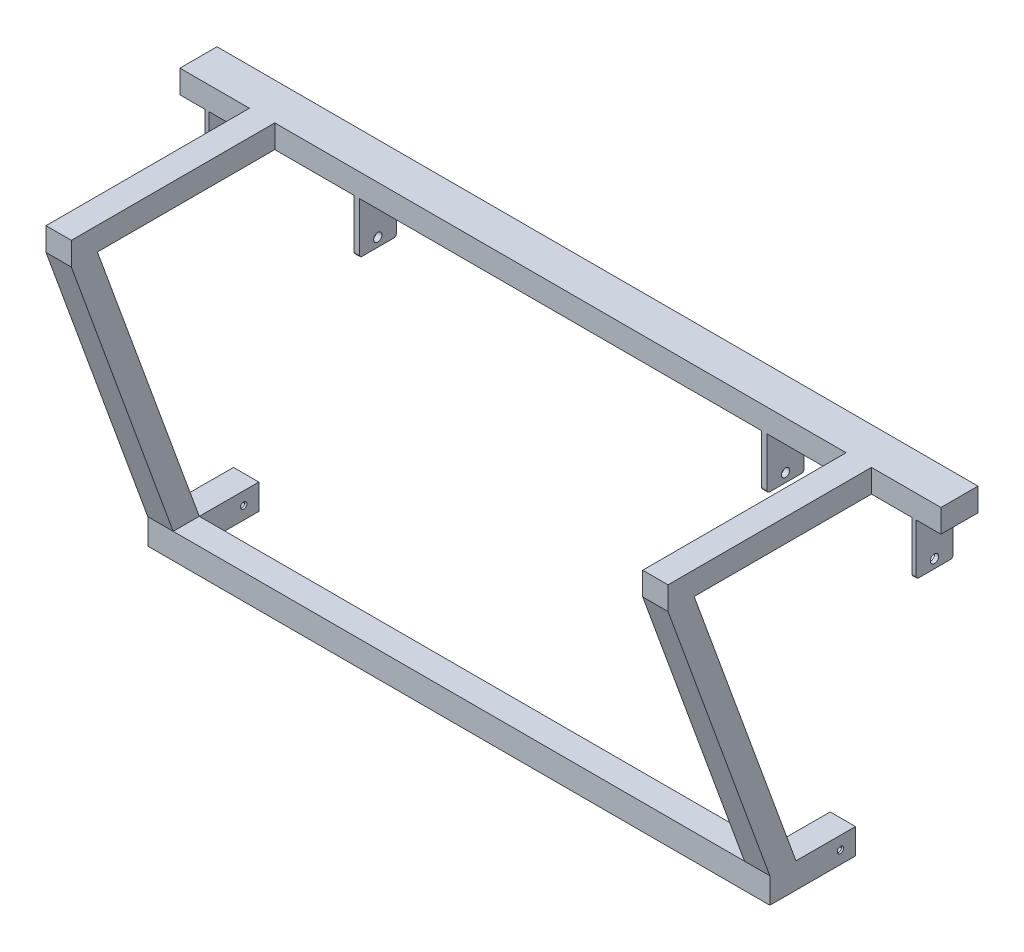
SolidWorks part; units mm, degrees
ref_plane "Front Plane" through (0, 0, 0) normal (0, 0, 1) x (1, 0, 0)
ref_plane "Top Plane" through (0, 0, 0) normal (0, 1, 0) x (1, 0, 0)
ref_plane "Right Plane" through (0, 0, 0) normal (1, 0, 0) x (0, 0, -1)
sketch "Sketch1" plane through (0, 0, 0) normal (0, 1, 0) x (1, 0, 0)
  line L1 (575, 28) -> (-575, 28)
  line L2 (575, 28) -> (575, -28)
  line L3 (575, -28) -> (-575, -28)
  line L4 (-575, 28) -> (-575, -28)
  line L5 (575, 28) -> (-575, -28) construction
  line L6 (575, -28) -> (-575, 28) construction
  point P0 (0, 0)
extrude "Boss-Extrude1" add sketch "Sketch1" against normal blind 35
sketch "Sketch2" plane through (0, 0, 28) normal (0, 0, 1) x (1, 0, 0)
  line L0 (0, -19.25) -> (0, 19.25) construction
  line L1 (-575, 0) -> (575, 0) construction
  line L2 (-470, 0) -> (-470, -35)
  line L3 (-575, -35) -> (575, -35) construction
  line L4 (-470, -35) -> (-431.7, -35)
  line L5 (-431.7, -35) -> (-431.7, 0)
  line L6 (-431.7, 0) -> (-470, 0)
  line L8 (431.7, 0) -> (470, 0)
  line L9 (431.7, -35) -> (431.7, 0)
  line L10 (470, -35) -> (431.7, -35)
  line L11 (470, 0) -> (470, -35)
extrude "Boss-Extrude2" add sketch "Sketch2" along normal blind 268
sketch "Sketch3" plane through (-470, 0, 0) normal (-1, 0, 0) x (0, 0, 1)
  line L0 (296, -35) -> (142.0909, -457.8617)
  line L2 (296, 0) -> (335.4, 0)
  line L3 (335.4, 0) -> (335.4, -35)
  line L4 (335.4, -35) -> (181.5154, -457.7945)
  line L6 (142.0909, -457.8617) -> (181.5154, -457.7945)
  line L7 (296, -35) -> (296, 0)
extrude "Boss-Extrude3" add sketch "Sketch3" against normal up to surface (38.3 mm away) up to face at (-431.7, -17.5, 162)
sketch "Sketch4" plane through (431.7, 0, 0) normal (-1, 0, 0) x (0, 0, 1)
  line L0 (296, 0) -> (335.4, 0)
  line L1 (335.4, 0) -> (335.4, -35)
  line L2 (335.4, -35) -> (181.5154, -457.7945)
  line L3 (181.5154, -457.7945) -> (142.0909, -457.8617)
  line L4 (142.0909, -457.8617) -> (296, -35)
  line L6 (296, 0) -> (296, -35)
extrude "Boss-Extrude4" add sketch "Sketch4" against normal up to surface (38.3 mm away) up to face at (470, -17.5, 162)
sketch "Sketch5" plane through (0, -458.1024, 0.7803) normal (0, -1, 0.0017) x (1, 0, 0)
  line L1 (470, 141.3109) -> (431.7, 141.3109)
  line L2 (470, 141.3109) -> (470, 180.7354)
  line L3 (470, 180.7354) -> (431.7, 180.7354)
  line L4 (431.7, 141.3109) -> (431.7, 180.7354)
extrude "Boss-Extrude5" add sketch "Sketch5" along normal blind 38.5
sketch "Sketch6" plane through (431.7, 0, 0) normal (-1, 0, 0) x (0, 0, 1)
  line L0 (142.0909, -457.8617) -> (181.5154, -457.7945)
  line L1 (181.5154, -457.7945) -> (181.581, -496.2945)
  line L2 (181.581, -496.2945) -> (142.1565, -496.3616)
  line L3 (142.1565, -496.3616) -> (142.0909, -457.8617)
extrude "Boss-Extrude6" add sketch "Sketch6" along normal up to surface (901.7 mm away) up to face at (-470, -145.808, 192.3438)
sketch "Sketch8" plane through (0, 0.2407, 141.3106) normal (0, -0.0017, -1) x (-1, 0, 0)
  line L0 (-470, -458.103) -> (-431.7, -458.103)
  line L1 (-431.7, -458.103) -> (-431.7, -496.603)
  line L2 (470, -496.603) -> (-470, -496.603) construction
  line L3 (-431.7, -496.603) -> (-470, -496.603)
  line L4 (-470, -496.603) -> (-470, -458.103)
  line L5 (0, 199.87) -> (0, -199.87) construction
  line L6 (431.7, -496.603) -> (470, -496.603)
  line L7 (431.7, -458.103) -> (431.7, -496.603)
  line L8 (470, -458.103) -> (431.7, -458.103)
  line L9 (470, -496.603) -> (470, -458.103)
extrude "Boss-Extrude7" add sketch "Sketch8" along normal blind 90
shell "Shell2" thickness 3 removed face at (-575, -17.5, 0)
sketch "Sketch13" plane through (-575, 0, 0) normal (-1, 0, 0) x (0, 0, 1)
  line L0 (-25, -32) -> (25, -32)
  line L1 (25, -32) -> (25, -3)
  line L2 (25, -3) -> (-25, -3)
  line L3 (-25, -3) -> (-25, -32)
extrude "Boss-Extrude8" add sketch "Sketch13" against normal blind 3
sketch "Sketch14" plane through (470, 0, 0) normal (1, 0, 0) x (0, 0, -1)
  line L1 (-52.1239, -477.2649) -> (-74.8739, -477.2649)
  line L2 (-52.0911, -458.015) -> (-52.1566, -496.5149) construction
  circle A0 centre (-74.8739, -477.2649) radius 4.75
extrude "Cut-Extrude1" cut sketch "Sketch14" against normal blind 1390 contours A0
sketch "Sketch15" plane through (0, 0, -28) normal (0, 0, -1) x (-1, 0, 0)
  line L0 (575, -35) -> (531.3, -35)
  line L1 (-575, -35) -> (575, -35) construction
  line L2 (531.3, -35) -> (531.3, -113)
  line L3 (531.3, -113) -> (537.3, -113)
  line L4 (537.3, -113) -> (537.3, -35)
  line L5 (537.3, -35) -> (531.3, -35)
  line L6 (0, 199.87) -> (0, -199.87) construction
  line L7 (304, -35) -> (304, -113)
  line L11 (304, -113) -> (312.1858, -113)
  line L12 (312.1858, -113) -> (312.1858, -35)
  line L13 (312.1858, -35) -> (304, -35)
  line L14 (-537.3, -35) -> (-531.3, -35)
  line L15 (-537.3, -113) -> (-537.3, -35)
  line L16 (-531.3, -113) -> (-537.3, -113)
  line L17 (-531.3, -35) -> (-531.3, -113)
  line L18 (-312.1858, -35) -> (-304, -35)
  line L19 (-312.1858, -113) -> (-312.1858, -35)
  line L20 (-304, -113) -> (-312.1858, -113)
  line L21 (-304, -35) -> (-304, -113)
  point P22 (0, 0)
  point P23 (0, 0)
  point P24 (0, 0)
  point P25 (312.1858, -35)
  line M7 (-575, -35) -> (575, -35)
extrude "Boss-Extrude10" add sketch "Sketch15" against normal up to surface (56 mm away) contours L11 L12 L7 M7 | L2 L3 L4 L5 | L15 L14 L17 L16 | L19 L18 L21 L20 region at (-308.0929, -74, -28) up to face at (-522.5, -17.5, 28)
fillet "Fillet2" radius 4 8 edges at (534.3, -113, -28) (534.3, -113, 28) (308.0929, -113, 28) (308.0929, -113, -28) (-308.0929, -113, -28) (-308.0929, -113, 28) (-534.3, -113, 28) (-534.3, -113, -28)
sketch "Sketch16" plane through (537.3, 0, 0) normal (1, 0, 0) x (0, 0, -1)
  line L0 (0, -113) -> (0, -99.8)
  line L1 (-24, -113) -> (24, -113) construction
  circle A0 centre (0, -99.8) radius 6.3
extrude "Cut-Extrude2" cut sketch "Sketch16" against normal blind 1390 contours A0 region at (537.3, -104.1288, -4.3288)
